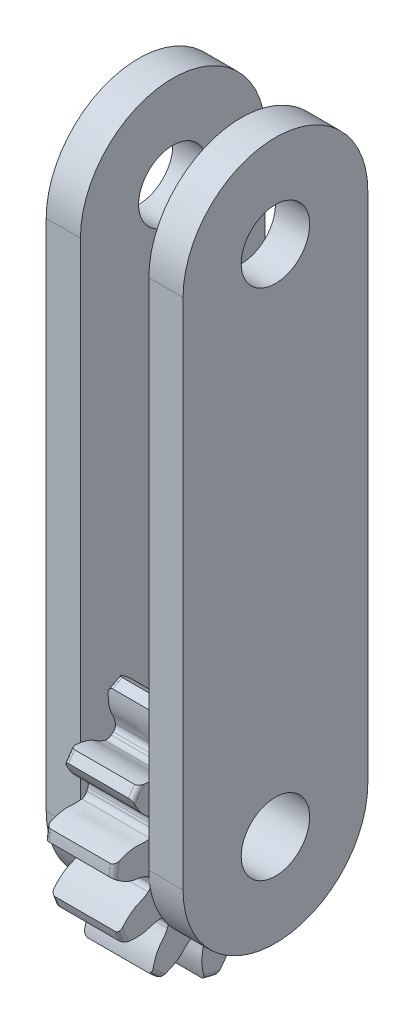
SolidWorks part; units mm, degrees
ref_plane "Front Plane" through (0, 0, 0) normal (0, 0, 1) x (1, 0, 0)
ref_plane "Top Plane" through (0, 0, 0) normal (0, 1, 0) x (1, 0, 0)
ref_plane "Right Plane" through (0, 0, 0) normal (1, 0, 0) x (0, 0, -1)
sketch "Sketch1" plane through (0, 0, 0) normal (0, 0, 1) x (1, 0, 0)
  line L0 (-4.5, 7.5) -> (-4.5, 0)
  line L1 (-4.5, 0) -> (4.5, 0)
  line L2 (4.5, 0) -> (4.5, 7.5)
  line L3 (4.5, 7.5) -> (-4.5, 7.5)
  line L4 (-4.5, 0) -> (4.5, 0) construction
revolve "Revolve1" add sketch "Sketch1" angle 360 about L4 reverse direction yes
sketch "Sketch2" plane through (-4.5, 0, 0) normal (-1, 0, 0) x (0, 0, 1)
  arc A0 (3.2016, 6.7823) -> (0.317, 7.4933) centre (0, 0) ccw
  arc A1 (0.9896, 5.2506) -> (1.5638, 5.109) centre (0, 0) cw
  spline S0 degree 3 poles (0.317, 7.4933) (0.3719, 7.409) (0.4239, 7.3227) (0.4724, 7.2346) (0.5595, 7.0765) (0.6363, 6.9119) (0.6977, 6.7422) (0.7757, 6.5269) (0.8305, 6.2966) (0.8268, 6.0677) (0.8235, 5.8657) (0.8584, 5.6614) (0.919, 5.4687) (0.9419, 5.3958) (0.966, 5.3233) (0.9896, 5.2506) knots -0.000301 -0.000301 -0.000301 -0.000301 0 0 0 0.000542 0.000542 0.000542 0.001235 0.001235 0.001235 0.001842 0.001842 0.001842 0.002069 0.002069 0.002069 0.002069
  spline S1 degree 3 poles (1.5638, 5.109) (1.6185, 5.1625) (1.6735, 5.2155) (1.7277, 5.2694) (1.8889, 5.4298) (2.0145, 5.6255) (2.1232, 5.8252) (2.251, 6.06) (2.4536, 6.2516) (2.6617, 6.4194) (2.7523, 6.4925) (2.8466, 6.5613) (2.9438, 6.6255) (3.0277, 6.6809) (3.1138, 6.7331) (3.2016, 6.7823) knots -0.000226 -0.000226 -0.000226 -0.000226 0 0 0 0.000682 0.000682 0.000682 0.001501 0.001501 0.001501 0.001854 0.001854 0.001854 0.002159 0.002159 0.002159 0.002159
extrude "Cut-Extrude1" cut sketch "Sketch2" against normal through all
sketch "Sketch3" plane through (-4.5, 0, 0) normal (-1, 0, 0) x (0, 0, 1)
  arc A0 (5.9868, 4.5176) -> (3.763, 6.4877) centre (0, 0) ccw
  arc A1 (3.3163, 4.1893) -> (3.759, 3.7971) centre (0, 0) cw
  spline S0 degree 3 poles (3.763, 6.4877) (3.7724, 6.3875) (3.7783, 6.2869) (3.7804, 6.1864) (3.784, 6.0059) (3.7755, 5.8245) (3.751, 5.6456) (3.72, 5.4188) (3.6615, 5.1894) (3.5519, 4.9884) (3.4551, 4.8111) (3.3911, 4.614) (3.3552, 4.4153) (3.3416, 4.34) (3.3292, 4.2646) (3.3163, 4.1893) knots -0.000301 -0.000301 -0.000301 -0.000301 0 0 0 0.000542 0.000542 0.000542 0.001235 0.001235 0.001235 0.001842 0.001842 0.001842 0.002069 0.002069 0.002069 0.002069
  spline S1 degree 3 poles (3.759, 3.7971) (3.8322, 3.819) (3.9056, 3.8404) (3.9786, 3.8629) (4.1959, 3.93) (4.398, 4.0449) (4.5871, 4.1713) (4.8093, 4.3198) (5.0778, 4.3952) (5.34, 4.4471) (5.4543, 4.4697) (5.5697, 4.4868) (5.6856, 4.4985) (5.7857, 4.5086) (5.8862, 4.5148) (5.9868, 4.5176) knots -0.000226 -0.000226 -0.000226 -0.000226 0 0 0 0.000682 0.000682 0.000682 0.001501 0.001501 0.001501 0.001854 0.001854 0.001854 0.002159 0.002159 0.002159 0.002159
extrude "Cut-Extrude2" cut sketch "Sketch3" against normal through all
sketch "Sketch4" plane through (-4.5, 0, 0) normal (-1, 0, 0) x (0, 0, 1)
  arc A0 (7.4004, 1.2179) -> (6.347, 3.9958) centre (0, 0) ccw
  arc A1 (4.8833, 2.1683) -> (5.093, 1.6152) centre (0, 0) cw
  spline S0 degree 3 poles (6.347, 3.9958) (6.3087, 3.9027) (6.2672, 3.8109) (6.2223, 3.7209) (6.1417, 3.5594) (6.0498, 3.4028) (5.945, 3.2558) (5.8122, 3.0694) (5.6537, 2.8934) (5.4633, 2.7664) (5.2952, 2.6543) (5.1469, 2.5096) (5.0227, 2.3503) (4.9758, 2.29) (4.9297, 2.229) (4.8833, 2.1683) knots -0.000301 -0.000301 -0.000301 -0.000301 0 0 0 0.000542 0.000542 0.000542 0.001235 0.001235 0.001235 0.001842 0.001842 0.001842 0.002069 0.002069 0.002069 0.002069
  spline S1 degree 3 poles (5.093, 1.6152) (5.168, 1.6006) (5.243, 1.5855) (5.3181, 1.5715) (5.5416, 1.5299) (5.774, 1.5377) (6.0001, 1.5617) (6.2659, 1.5899) (6.5388, 1.532) (6.795, 1.4561) (6.9067, 1.423) (7.0169, 1.3845) (7.1249, 1.341) (7.2182, 1.3034) (7.3101, 1.2622) (7.4004, 1.2179) knots -0.000226 -0.000226 -0.000226 -0.000226 0 0 0 0.000682 0.000682 0.000682 0.001501 0.001501 0.001501 0.001854 0.001854 0.001854 0.002159 0.002159 0.002159 0.002159
extrude "Cut-Extrude3" cut sketch "Sketch4" against normal through all
sketch "Sketch5" plane through (-4.5, 0, 0) normal (-1, 0, 0) x (0, 0, 1)
  arc A0 (7.1188, -2.3607) -> (7.4769, 0.5885) centre (0, 0) ccw
  arc A1 (5.3316, -0.3495) -> (5.2603, -0.9366) centre (0, 0) cw
  spline S0 degree 3 poles (7.4769, 0.5885) (7.3998, 0.5239) (7.3204, 0.4619) (7.2388, 0.4031) (7.0923, 0.2975) (6.9382, 0.2015) (6.7771, 0.12) (6.5728, 0.0167) (6.3508, -0.0655) (6.1231, -0.0894) (5.9222, -0.1105) (5.7236, -0.1697) (5.5396, -0.2531) (5.47, -0.2847) (5.4009, -0.3173) (5.3316, -0.3495) knots -0.000301 -0.000301 -0.000301 -0.000301 0 0 0 0.000542 0.000542 0.000542 0.001235 0.001235 0.001235 0.001842 0.001842 0.001842 0.002069 0.002069 0.002069 0.002069
  spline S1 degree 3 poles (5.2603, -0.9366) (5.3199, -0.9844) (5.3792, -1.0327) (5.4392, -1.08) (5.6179, -1.2207) (5.8273, -1.3217) (6.0386, -1.4056) (6.2871, -1.5041) (6.5017, -1.6822) (6.6934, -1.8685) (6.7769, -1.9497) (6.8565, -2.035) (6.932, -2.1237) (6.9971, -2.2003) (7.0594, -2.2796) (7.1188, -2.3607) knots -0.000226 -0.000226 -0.000226 -0.000226 0 0 0 0.000682 0.000682 0.000682 0.001501 0.001501 0.001501 0.001854 0.001854 0.001854 0.002159 0.002159 0.002159 0.002159
extrude "Cut-Extrude4" cut sketch "Sketch5" against normal through all
sketch "Sketch6" plane through (-4.5, 0, 0) normal (-1, 0, 0) x (0, 0, 1)
  arc A0 (5.2063, -5.3986) -> (6.8939, -2.9536) centre (0, 0) ccw
  arc A1 (4.5585, -2.7871) -> (4.2225, -3.2739) centre (0, 0) cw
  spline S0 degree 3 poles (6.8939, -2.9536) (6.7956, -2.975) (6.6965, -2.993) (6.5969, -3.0071) (6.4182, -3.0325) (6.2371, -3.0459) (6.0566, -3.0432) (5.8277, -3.0398) (5.5929, -3.0093) (5.3802, -2.9247) (5.1925, -2.85) (4.9891, -2.8102) (4.7875, -2.7985) (4.7112, -2.7941) (4.6348, -2.7909) (4.5585, -2.7871) knots -0.000301 -0.000301 -0.000301 -0.000301 0 0 0 0.000542 0.000542 0.000542 0.001235 0.001235 0.001235 0.001842 0.001842 0.001842 0.002069 0.002069 0.002069 0.002069
  spline S1 degree 3 poles (4.2225, -3.2739) (4.2531, -3.3439) (4.2831, -3.4142) (4.3143, -3.484) (4.4071, -3.6916) (4.5456, -3.8784) (4.6938, -4.0509) (4.868, -4.2536) (4.9753, -4.511) (5.0584, -4.765) (5.0946, -4.8757) (5.1255, -4.9883) (5.151, -5.1019) (5.1731, -5.2) (5.1914, -5.2991) (5.2063, -5.3986) knots -0.000226 -0.000226 -0.000226 -0.000226 0 0 0 0.000682 0.000682 0.000682 0.001501 0.001501 0.001501 0.001854 0.001854 0.001854 0.002159 0.002159 0.002159 0.002159
extrude "Cut-Extrude5" cut sketch "Sketch6" against normal through all
sketch "Sketch7" plane through (-4.5, 0, 0) normal (-1, 0, 0) x (0, 0, 1)
  arc A0 (2.7411, -4.5863) -> (2.2173, -4.8612) centre (0, 0) cw
  arc A1 (2.1011, -7.1997) -> (4.7317, -5.819) centre (0, 0) ccw
  spline S0 degree 3 poles (4.7317, -5.819) (4.6347, -5.7923) (4.5386, -5.7622) (4.4438, -5.7284) (4.2738, -5.6679) (4.1072, -5.5955) (3.9486, -5.5093) (3.7476, -5.3999) (3.5538, -5.2638) (3.4048, -5.09) (3.2733, -4.9367) (3.1117, -4.8069) (2.9386, -4.7028) (2.8731, -4.6635) (2.8069, -4.6251) (2.7411, -4.5863) knots -0.000301 -0.000301 -0.000301 -0.000301 0 0 0 0.000542 0.000542 0.000542 0.001235 0.001235 0.001235 0.001842 0.001842 0.001842 0.002069 0.002069 0.002069 0.002069
  spline S1 degree 3 poles (2.2173, -4.8612) (2.2119, -4.9374) (2.2059, -5.0136) (2.2011, -5.0899) (2.1867, -5.3168) (2.2225, -5.5466) (2.2736, -5.7681) (2.3336, -6.0286) (2.309, -6.3064) (2.2645, -6.57) (2.2452, -6.6848) (2.2202, -6.7988) (2.19, -6.9113) (2.164, -7.0085) (2.1341, -7.1047) (2.1011, -7.1997) knots -0.000226 -0.000226 -0.000226 -0.000226 0 0 0 0.000682 0.000682 0.000682 0.001501 0.001501 0.001501 0.001854 0.001854 0.001854 0.002159 0.002159 0.002159 0.002159
extrude "Cut-Extrude6" cut sketch "Sketch7" against normal through all
sketch "Sketch8" plane through (-4.5, 0, 0) normal (-1, 0, 0) x (0, 0, 1)
  arc A0 (-1.4854, -7.3514) -> (1.4854, -7.3514) centre (0, 0) ccw
  arc A1 (0.2957, -5.3348) -> (-0.2957, -5.3348) centre (0, 0) cw
  spline S0 degree 3 poles (1.4854, -7.3514) (1.412, -7.2827) (1.3409, -7.2113) (1.2727, -7.1374) (1.1503, -7.0048) (1.0363, -6.8633) (0.9361, -6.7132) (0.8089, -6.5229) (0.7005, -6.3123) (0.6493, -6.0892) (0.6041, -5.8924) (0.5214, -5.7024) (0.4165, -5.5298) (0.3767, -5.4645) (0.336, -5.3998) (0.2957, -5.3348) knots -0.000301 -0.000301 -0.000301 -0.000301 0 0 0 0.000542 0.000542 0.000542 0.001235 0.001235 0.001235 0.001842 0.001842 0.001842 0.002069 0.002069 0.002069 0.002069
  spline S1 degree 3 poles (-0.2957, -5.3348) (-0.336, -5.3998) (-0.3767, -5.4645) (-0.4165, -5.5298) (-0.5346, -5.724) (-0.6097, -5.9441) (-0.6674, -6.164) (-0.7353, -6.4226) (-0.8862, -6.6571) (-1.0481, -6.8698) (-1.1186, -6.9625) (-1.1937, -7.0518) (-1.2727, -7.1374) (-1.3409, -7.2113) (-1.412, -7.2827) (-1.4854, -7.3514) knots -0.000226 -0.000226 -0.000226 -0.000226 0 0 0 0.000682 0.000682 0.000682 0.001501 0.001501 0.001501 0.001854 0.001854 0.001854 0.002159 0.002159 0.002159 0.002159
extrude "Cut-Extrude7" cut sketch "Sketch8" against normal through all
sketch "Sketch9" plane through (-4.5, 0, 0) normal (-1, 0, 0) x (0, 0, 1)
  arc A0 (-4.7317, -5.819) -> (-2.1011, -7.1997) centre (0, 0) ccw
  arc A1 (-2.2173, -4.8612) -> (-2.7411, -4.5863) centre (0, 0) cw
  spline S0 degree 3 poles (-2.1011, -7.1997) (-2.1341, -7.1047) (-2.164, -7.0085) (-2.19, -6.9113) (-2.2368, -6.737) (-2.2719, -6.5588) (-2.291, -6.3793) (-2.3151, -6.1516) (-2.3132, -5.9149) (-2.2549, -5.6935) (-2.2034, -5.4982) (-2.1883, -5.2915) (-2.2011, -5.0899) (-2.2059, -5.0136) (-2.2119, -4.9374) (-2.2173, -4.8612) knots -0.000301 -0.000301 -0.000301 -0.000301 0 0 0 0.000542 0.000542 0.000542 0.001235 0.001235 0.001235 0.001842 0.001842 0.001842 0.002069 0.002069 0.002069 0.002069
  spline S1 degree 3 poles (-2.7411, -4.5863) (-2.8069, -4.6251) (-2.8731, -4.6635) (-2.9386, -4.7028) (-3.1335, -4.8199) (-3.3022, -4.9799) (-3.4555, -5.1478) (-3.6358, -5.3452) (-3.8784, -5.4827) (-4.1206, -5.5959) (-4.2261, -5.6452) (-4.3341, -5.6894) (-4.4438, -5.7284) (-4.5386, -5.7622) (-4.6347, -5.7923) (-4.7317, -5.819) knots -0.000226 -0.000226 -0.000226 -0.000226 0 0 0 0.000682 0.000682 0.000682 0.001501 0.001501 0.001501 0.001854 0.001854 0.001854 0.002159 0.002159 0.002159 0.002159
extrude "Cut-Extrude8" cut sketch "Sketch9" against normal through all
sketch "Sketch10" plane through (-4.5, 0, 0) normal (-1, 0, 0) x (0, 0, 1)
  arc A0 (-6.8939, -2.9536) -> (-5.2063, -5.3986) centre (0, 0) ccw
  arc A1 (-4.2225, -3.2739) -> (-4.5585, -2.7871) centre (0, 0) cw
  spline S0 degree 3 poles (-5.2063, -5.3986) (-5.1914, -5.2991) (-5.1731, -5.2) (-5.151, -5.1019) (-5.1114, -4.9258) (-5.0597, -4.7517) (-4.9931, -4.5839) (-4.9088, -4.3711) (-4.797, -4.1623) (-4.6425, -3.9935) (-4.5061, -3.8444) (-4.3968, -3.6684) (-4.3143, -3.484) (-4.2831, -3.4142) (-4.2531, -3.3439) (-4.2225, -3.2739) knots -0.000301 -0.000301 -0.000301 -0.000301 0 0 0 0.000542 0.000542 0.000542 0.001235 0.001235 0.001235 0.001842 0.001842 0.001842 0.002069 0.002069 0.002069 0.002069
  spline S1 degree 3 poles (-4.5585, -2.7871) (-4.6348, -2.7909) (-4.7112, -2.7941) (-4.7875, -2.7985) (-5.0145, -2.8117) (-5.2383, -2.8749) (-5.452, -2.9523) (-5.7034, -3.0433) (-5.9821, -3.0523) (-6.2491, -3.04) (-6.3655, -3.0346) (-6.4816, -3.0235) (-6.5969, -3.0071) (-6.6965, -2.993) (-6.7956, -2.975) (-6.8939, -2.9536) knots -0.000226 -0.000226 -0.000226 -0.000226 0 0 0 0.000682 0.000682 0.000682 0.001501 0.001501 0.001501 0.001854 0.001854 0.001854 0.002159 0.002159 0.002159 0.002159
extrude "Cut-Extrude9" cut sketch "Sketch10" against normal through all
sketch "Sketch11" plane through (-4.5, 0, 0) normal (-1, 0, 0) x (0, 0, 1)
  arc A0 (-7.4769, 0.5885) -> (-7.1188, -2.3607) centre (0, 0) ccw
  arc A1 (-5.2603, -0.9366) -> (-5.3316, -0.3495) centre (0, 0) cw
  spline S0 degree 3 poles (-7.1188, -2.3607) (-7.0594, -2.2796) (-6.9971, -2.2003) (-6.932, -2.1237) (-6.815, -1.9862) (-6.6883, -1.8561) (-6.5514, -1.7384) (-6.3779, -1.5892) (-6.1819, -1.4563) (-5.9666, -1.3786) (-5.7766, -1.31) (-5.5979, -1.205) (-5.4392, -1.08) (-5.3792, -1.0327) (-5.3199, -0.9844) (-5.2603, -0.9366) knots -0.000301 -0.000301 -0.000301 -0.000301 0 0 0 0.000542 0.000542 0.000542 0.001235 0.001235 0.001235 0.001842 0.001842 0.001842 0.002069 0.002069 0.002069 0.002069
  spline S1 degree 3 poles (-5.3316, -0.3495) (-5.4009, -0.3173) (-5.47, -0.2847) (-5.5396, -0.2531) (-5.7467, -0.1593) (-5.9743, -0.1112) (-6.1995, -0.0804) (-6.4644, -0.0442) (-6.7154, 0.0773) (-6.9461, 0.2124) (-7.0466, 0.2712) (-7.1443, 0.335) (-7.2388, 0.4031) (-7.3204, 0.4619) (-7.3998, 0.5239) (-7.4769, 0.5885) knots -0.000226 -0.000226 -0.000226 -0.000226 0 0 0 0.000682 0.000682 0.000682 0.001501 0.001501 0.001501 0.001854 0.001854 0.001854 0.002159 0.002159 0.002159 0.002159
extrude "Cut-Extrude10" cut sketch "Sketch11" against normal through all
sketch "Sketch12" plane through (-4.5, 0, 0) normal (-1, 0, 0) x (0, 0, 1)
  arc A0 (-6.347, 3.9958) -> (-7.4004, 1.2179) centre (0, 0) ccw
  arc A1 (-5.093, 1.6152) -> (-4.8833, 2.1683) centre (0, 0) cw
  spline S0 degree 3 poles (-7.4004, 1.2179) (-7.3101, 1.2622) (-7.2182, 1.3034) (-7.1249, 1.341) (-6.9575, 1.4084) (-6.7848, 1.4648) (-6.6089, 1.5053) (-6.3859, 1.5568) (-6.1506, 1.5834) (-5.9238, 1.5521) (-5.7237, 1.5246) (-5.5167, 1.5346) (-5.3181, 1.5715) (-5.243, 1.5855) (-5.168, 1.6006) (-5.093, 1.6152) knots -0.000301 -0.000301 -0.000301 -0.000301 0 0 0 0.000542 0.000542 0.000542 0.001235 0.001235 0.001235 0.001842 0.001842 0.001842 0.002069 0.002069 0.002069 0.002069
  spline S1 degree 3 poles (-4.8833, 2.1683) (-4.9297, 2.229) (-4.9758, 2.29) (-5.0227, 2.3503) (-5.1625, 2.5296) (-5.3416, 2.6779) (-5.5268, 2.8099) (-5.7445, 2.965) (-5.9102, 3.1893) (-6.0517, 3.416) (-6.1134, 3.5148) (-6.1703, 3.6167) (-6.2223, 3.7209) (-6.2672, 3.8109) (-6.3087, 3.9027) (-6.347, 3.9958) knots -0.000226 -0.000226 -0.000226 -0.000226 0 0 0 0.000682 0.000682 0.000682 0.001501 0.001501 0.001501 0.001854 0.001854 0.001854 0.002159 0.002159 0.002159 0.002159
extrude "Cut-Extrude11" cut sketch "Sketch12" against normal through all
sketch "Sketch13" plane through (-4.5, 0, 0) normal (-1, 0, 0) x (0, 0, 1)
  arc A0 (-3.763, 6.4877) -> (-5.9868, 4.5176) centre (0, 0) ccw
  arc A1 (-3.759, 3.7971) -> (-3.3163, 4.1893) centre (0, 0) cw
  spline S0 degree 3 poles (-5.9868, 4.5176) (-5.8862, 4.5148) (-5.7857, 4.5086) (-5.6856, 4.4985) (-5.506, 4.4804) (-5.3269, 4.45) (-5.1523, 4.4042) (-4.9309, 4.3461) (-4.7102, 4.2603) (-4.5239, 4.1273) (-4.3596, 4.0099) (-4.1716, 3.9225) (-3.9786, 3.8629) (-3.9056, 3.8404) (-3.8322, 3.819) (-3.759, 3.7971) knots -0.000301 -0.000301 -0.000301 -0.000301 0 0 0 0.000542 0.000542 0.000542 0.001235 0.001235 0.001235 0.001842 0.001842 0.001842 0.002069 0.002069 0.002069 0.002069
  spline S1 degree 3 poles (-3.3163, 4.1893) (-3.3292, 4.2646) (-3.3416, 4.34) (-3.3552, 4.4153) (-3.3956, 4.639) (-3.4853, 4.8535) (-3.5879, 5.0564) (-3.7086, 5.295) (-3.7511, 5.5706) (-3.771, 5.8371) (-3.7797, 5.9533) (-3.7827, 6.0699) (-3.7804, 6.1864) (-3.7783, 6.2869) (-3.7724, 6.3875) (-3.763, 6.4877) knots -0.000226 -0.000226 -0.000226 -0.000226 0 0 0 0.000682 0.000682 0.000682 0.001501 0.001501 0.001501 0.001854 0.001854 0.001854 0.002159 0.002159 0.002159 0.002159
extrude "Cut-Extrude12" cut sketch "Sketch13" against normal through all
sketch "Sketch14" plane through (-4.5, 0, 0) normal (-1, 0, 0) x (0, 0, 1)
  arc A0 (-0.317, 7.4933) -> (-3.2016, 6.7823) centre (0, 0) ccw
  arc A1 (-1.5638, 5.109) -> (-0.9896, 5.2506) centre (0, 0) cw
  spline S0 degree 3 poles (-3.2016, 6.7823) (-3.1138, 6.7331) (-3.0277, 6.6809) (-2.9438, 6.6255) (-2.7932, 6.5259) (-2.6487, 6.4159) (-2.5154, 6.2941) (-2.3464, 6.1398) (-2.1908, 5.9613) (-2.0877, 5.7569) (-1.9967, 5.5766) (-1.8709, 5.4119) (-1.7277, 5.2694) (-1.6735, 5.2155) (-1.6185, 5.1625) (-1.5638, 5.109) knots -0.000301 -0.000301 -0.000301 -0.000301 0 0 0 0.000542 0.000542 0.000542 0.001235 0.001235 0.001235 0.001842 0.001842 0.001842 0.002069 0.002069 0.002069 0.002069
  spline S1 degree 3 poles (-0.9896, 5.2506) (-0.966, 5.3233) (-0.9419, 5.3958) (-0.919, 5.4687) (-0.8508, 5.6856) (-0.8305, 5.9173) (-0.8271, 6.1446) (-0.8231, 6.4119) (-0.7327, 6.6757) (-0.6264, 6.921) (-0.5801, 7.0279) (-0.5286, 7.1326) (-0.4724, 7.2346) (-0.4239, 7.3227) (-0.3719, 7.409) (-0.317, 7.4933) knots -0.000226 -0.000226 -0.000226 -0.000226 0 0 0 0.000682 0.000682 0.000682 0.001501 0.001501 0.001501 0.001854 0.001854 0.001854 0.002159 0.002159 0.002159 0.002159
extrude "Cut-Extrude13" cut sketch "Sketch14" against normal through all
fillet "Fillet2" radius 0.39 26 edges at (0, -4.8612, -2.2173) (0, 4.1893, -3.3163) (0, -0.3495, -5.3316) (0, 5.2506, 0.9896) (0, -5.3348, 0.2957) (0, 5.109, 1.5638) (0, -2.7871, -4.5585) (0, 4.1893, 3.3163) (0, 2.1683, -4.8833) (0, 3.7971, 3.759) (0, 5.2506, -0.9896) (0, 2.1683, 4.8833) (0, -5.3348, -0.2957) (0, 1.6152, 5.093) (0, -4.5863, -2.7411) (0, -0.3495, 5.3316) (0, -0.9366, -5.2603) (0, -0.9366, 5.2603) (0, 1.6152, -5.093) (0, -2.7871, 4.5585) (0, 3.7971, -3.759) (0, -3.2739, 4.2225) (0, 5.109, -1.5638) (0, -4.5863, 2.7411) (0, -4.8612, 2.2173) (0, -3.2739, -4.2225) tangent propagation no
sketch "Sketch15" plane through (0, 0, 0) normal (0, 1, 0) x (1, 0, 0)
  line L0 (-4.5, 7.4004) -> (-4.5, 5.3181) construction
  line L1 (-9.792, 10.9751) -> (-2.5, 10.9751)
  line L2 (-9.792, 10.9751) -> (-9.792, -9.9016)
  line L3 (-9.792, -9.9016) -> (-2.5, -9.9016)
  line L4 (-2.5, 10.9751) -> (-2.5, -9.9016)
  line L5 (2.5, 10.9751) -> (9.607, 10.9751)
  line L6 (2.5, 10.9751) -> (2.5, -9.9016)
  line L7 (2.5, -9.9016) -> (9.607, -9.9016)
  line L8 (9.607, 10.9751) -> (9.607, -9.9016)
  line L9 (4.5, 3.9786) -> (4.5, 5.9868) construction
  dimension "D1" = 2
  dimension "D2" = 2
extrude "Cut-Extrude14" cut sketch "Sketch15" against normal mid plane 20
sketch "Sketch18" plane through (0, 0, 0) normal (0, 0, 1) x (1, 0, 0)
  line L0 (2.5, -5.3986) -> (2.5, -3.484) construction
  line L1 (1.5, 9.5135) -> (5.8934, 9.5135)
  line L2 (1.5, 9.5135) -> (1.5, -8.8471)
  line L3 (1.5, -8.8471) -> (5.8934, -8.8471)
  line L4 (5.8934, 9.5135) -> (5.8934, -8.8471)
  dimension "D1" = 1
extrude "Cut-Extrude15" cut sketch "Sketch18" against normal through all and the other way blind 10
fillet "Fillet4" radius 0.25 26 edges at (-2.5, 4.2605, 6.1724) (1.5, 4.2605, 6.1724) (1.5, 0.904, 7.4453) (-2.5, 0.904, 7.4453) (-2.5, -2.6595, 7.0126) (1.5, -2.6595, 7.0126) (1.5, -5.6138, 4.9734) (-2.5, -5.6138, 4.9734) (-2.5, -7.2821, 1.7949) (1.5, -7.2821, 1.7949) (1.5, -7.2821, -1.7949) (-2.5, -7.2821, -1.7949) (1.5, -5.6138, -4.9734) (-2.5, -5.6138, -4.9734) (1.5, -2.6595, -7.0126) (-2.5, -2.6595, -7.0126) (-2.5, 0.904, -7.4453) (1.5, 0.904, -7.4453) (1.5, 4.2605, -6.1724) (-2.5, 4.2605, -6.1724) (-2.5, 6.6409, -3.4854) (1.5, 6.6409, -3.4854) (1.5, 7.5, 0) (-2.5, 7.5, 0) (1.5, 6.6409, 3.4854) (-2.5, 6.6409, 3.4854) tangent propagation no
sketch "Sketch19" plane through (-2.5, 0, 0) normal (-1, 0, 0) x (0, 0, 1)
  line L0 (5.4, 0) -> (5.4, 30)
  line L1 (-5.4, 0) -> (-5.4, 30)
  arc A0 (-5.4, 0) -> (5.4, 0) centre (0, 0) ccw
  circle A1 centre (0, 30) radius 2
  arc A3 (5.4, 30) -> (-5.4, 30) centre (0, 30) ccw
  dimension "D1" = 10.8
  dimension "D4" = 10.8
extrude "Boss-Extrude1" add sketch "Sketch19" along normal blind 2
extrude "Boss-Extrude2" add sketch "Sketch19<2>" against normal blind 2 from offset 4 offset against normal yes
sketch "Sketch19<2>" plane through (-2.5, 0, 0) normal (-1, 0, 0) x (0, 0, 1) same geometry as "Sketch19"
sketch "Sketch20" plane through (0, 0, 0) normal (1, 0, 0) x (0, 0, -1)
  circle A0 centre (0, 0) radius 2
extrude "Cut-Extrude16" cut sketch "Sketch20" against normal mid plane 10
